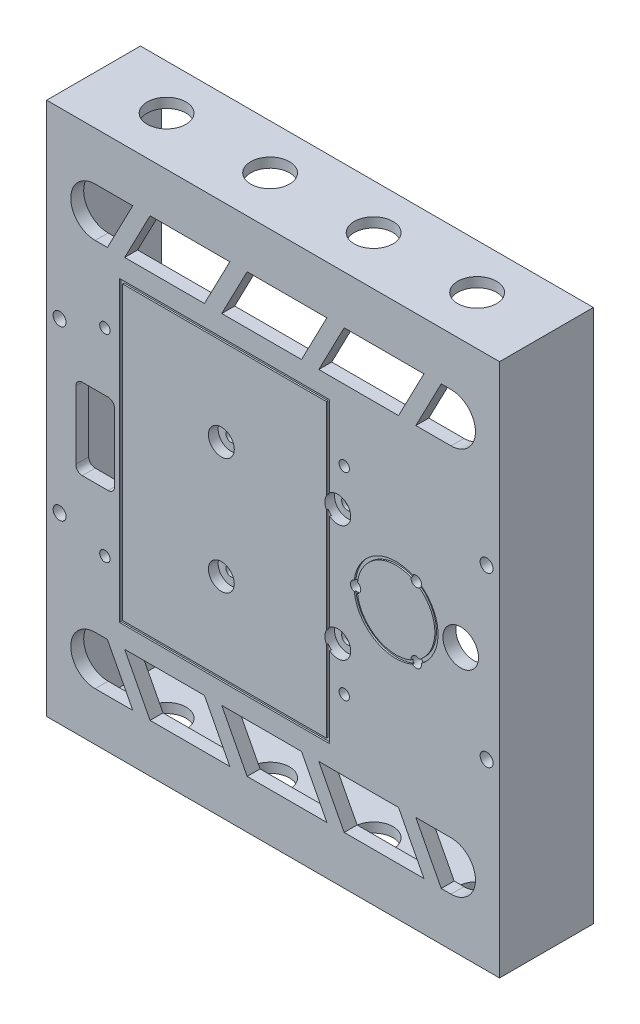
SolidWorks part; units mm, degrees
ref_plane "前视基准面" through (0, 0, 0) normal (0, 0, 1) x (1, 0, 0)
ref_plane "上视基准面" through (0, 0, 0) normal (0, 1, 0) x (1, 0, 0)
ref_plane "右视基准面" through (0, 0, 0) normal (1, 0, 0) x (0, 0, -1)
other "Configuration Table"
sketch "草图1" plane through (0, 0, 0) normal (0, 0, 1) x (1, 0, 0)
  line L0 (-109.8258, 0) -> (108.2292, 0) construction
  line L1 (-70, -82.5) -> (70, -82.5)
  line L2 (-70, -82.5) -> (-70, 82.5)
  line L3 (-70, 82.5) -> (70, 82.5)
  line L4 (70, -82.5) -> (70, 82.5)
  line L5 (-70, -82.5) -> (70, 82.5) construction
  line L6 (-70, 82.5) -> (70, -82.5) construction
  line L13 (-59, -12.5) -> (-51, -12.5)
  line L16 (0, 87.3901) -> (0, -88.6403) construction
  line L17 (-54.4075, -60) -> (62.7091, -60) construction
  line L20 (-61, -10.5) -> (-61, 10.5)
  line L21 (-59, 12.5) -> (-51, 12.5)
  line L22 (-49, -10.5) -> (-49, 10.5)
  line L23 (-61, -12.5) -> (-49, 12.5) construction
  line L24 (-61, 12.5) -> (-49, -12.5) construction
  line L107 (-50.0297, -53) -> (45.5374, -53) construction
  line L108 (-55, -60) -> (55, -60) construction
  line L109 (-55, -52.4529) -> (-51.2224, -52.4529)
  line L110 (-55, -67.5471) -> (-43.3736, -67.5471)
  line L112 (-51.2224, -52.4529) -> (-43.3736, -67.5471)
  line L113 (-45.8742, -52.4529) -> (-38.0254, -67.5471)
  line L116 (-21.2224, -52.4529) -> (-13.3736, -67.5471)
  line L118 (-15.8742, -52.4529) -> (-8.0254, -67.5471)
  line L120 (8.7776, -52.4529) -> (16.6264, -67.5471)
  line L122 (14.1258, -52.4529) -> (21.9746, -67.5471)
  line L124 (38.7776, -52.4529) -> (46.6264, -67.5471)
  line L126 (44.1258, -52.4529) -> (51.9746, -67.5471)
  line L127 (-45.8742, -52.4529) -> (-21.2224, -52.4529)
  line L128 (-38.0254, -67.5471) -> (-13.3736, -67.5471)
  line L129 (-8.0254, -67.5471) -> (16.6264, -67.5471)
  line L130 (-15.8742, -52.4529) -> (8.7776, -52.4529)
  line L131 (14.1258, -52.4529) -> (38.7776, -52.4529)
  line L132 (21.9746, -67.5471) -> (46.6264, -67.5471)
  line L133 (44.1258, -52.4529) -> (55, -52.4529)
  line L134 (51.9746, -67.5471) -> (55, -67.5471)
  line L135 (51.9746, 67.5471) -> (55, 67.5471)
  line L136 (44.1258, 52.4529) -> (51.9746, 67.5471)
  line L137 (44.1258, 52.4529) -> (55, 52.4529)
  line L138 (14.1258, 52.4529) -> (38.7776, 52.4529)
  line L139 (38.7776, 52.4529) -> (46.6264, 67.5471)
  line L140 (21.9746, 67.5471) -> (46.6264, 67.5471)
  line L141 (14.1258, 52.4529) -> (21.9746, 67.5471)
  line L142 (-15.8742, 52.4529) -> (8.7776, 52.4529)
  line L143 (8.7776, 52.4529) -> (16.6264, 67.5471)
  line L144 (-8.0254, 67.5471) -> (16.6264, 67.5471)
  line L145 (-15.8742, 52.4529) -> (-8.0254, 67.5471)
  line L146 (-45.8742, 52.4529) -> (-21.2224, 52.4529)
  line L147 (-21.2224, 52.4529) -> (-13.3736, 67.5471)
  line L148 (-38.0254, 67.5471) -> (-13.3736, 67.5471)
  line L149 (-45.8742, 52.4529) -> (-38.0254, 67.5471)
  line L150 (-55, 67.5471) -> (-43.3736, 67.5471)
  line L151 (-55, 52.4529) -> (-51.2224, 52.4529)
  line L152 (-51.2224, 52.4529) -> (-43.3736, 67.5471)
  line L153 (-16, 18) -> (20, 18) construction
  circle A5 centre (-66, 26) radius 2
  circle A10 centre (-66, -26) radius 2
  circle A15 centre (58, 0) radius 5.5
  arc A17 (-51, -12.5) -> (-49, -10.5) centre (-51, -10.5) ccw
  arc A18 (-59, -12.5) -> (-61, -10.5) centre (-59, -10.5) cw
  arc A19 (-51, 12.5) -> (-49, 10.5) centre (-51, 10.5) cw
  arc A20 (-61, 10.5) -> (-59, 12.5) centre (-59, 10.5) cw
  circle A24 centre (66, -26) radius 2
  circle A25 centre (66, 26) radius 2
  circle A29 centre (-16, 18) radius 1.6
  circle A35 centre (-52, 30.55) radius 1.6
  circle A37 centre (-52, -30.55) radius 1.6
  circle A41 centre (38, 0) radius 12.5 construction
  circle A42 centre (25.5, 0) radius 1.6
  circle A43 centre (44.25, 10.8253) radius 1.6
  circle A44 centre (44.25, -10.8253) radius 1.6
  arc A47 (-55, -52.4529) -> (-55, -67.5471) centre (-55, -60) ccw
  arc A48 (55, -67.5471) -> (55, -52.4529) centre (55, -60) ccw
  arc A49 (55, 67.5471) -> (55, 52.4529) centre (55, 60) cw
  arc A50 (-55, 52.4529) -> (-55, 67.5471) centre (-55, 60) cw
  circle A51 centre (20, 18) radius 1.8189
  circle A52 centre (20, -18) radius 1.8189
  circle A53 centre (-16, -18) radius 1.6
  circle A54 centre (22, 30.55) radius 1.6
  circle A55 centre (22, -30.55) radius 1.6
  point P0 (0, 0)
  point P12 (0, 0)
  point P13 (-55, 0)
  point P24 (0, 0)
  point P26 (0, -60)
  point P35 (0, 57)
  point P46 (0, -57)
  point P53 (38, 0)
  point P69 (0, 0)
  point P73 (38, 0)
  point P114 (0, 0)
  dimension "D3" = 26
  dimension "D6" = 38
  dimension "D7" = 4
  dimension "D8" = 9
  dimension "D10" = 25
  dimension "D11" = 70
  dimension "D12" = 3.2
  dimension "D13" = 2
  dimension "D14" = 3
  dimension "D15" = 25
  dimension "D17" = 18
  dimension "D18" = 36
  dimension "D21" = 4
  dimension "D22" = 74
  dimension "D23" = 3.2
  dimension "D24" = 30.55
  dimension "D25" = 18
  dimension "D26" = 58
  dimension "D28" = 4
  dimension "D29" = 11
  dimension "D19" = 16
  dimension "D1" = 140
  dimension "D2" = 165
  dimension "D9" = 12
  dimension "D20" = 60
  dimension "D16" = 82.5
extrude "凸台-拉伸1" add sketch "草图1" along normal blind 4
sketch "草图2" plane through (0, 0, 4) normal (0, 0, 1) x (1, 0, 0)
sketch "草图3" plane through (0, 0, 4) normal (0, 0, 1) x (1, 0, 0)
  line L1 (-47.5, 46.05) -> (17.5, 46.05)
  line L2 (-47.5, 46.05) -> (-47.5, -46.05)
  line L3 (-47.5, -46.05) -> (17.5, -46.05)
  line L4 (17.5, 46.05) -> (17.5, -46.05)
  line L5 (-46.5, 45.05) -> (16.5, 45.05)
  line L6 (-46.5, 45.05) -> (-46.5, -45.05)
  line L7 (-46.5, -45.05) -> (16.5, -45.05)
  line L8 (16.5, 45.05) -> (16.5, -45.05)
  circle A0 centre (-52, 30.55) radius 1.6 construction
  circle A2 centre (22, 30.55) radius 1.6 construction
  circle A3 centre (-52, -30.55) radius 1.6 construction
  dimension "D3" = 4.5
  dimension "D7" = 14.5
  dimension "D8" = 15.5
  dimension "D1" = 5.5
  dimension "D2" = 4.5
  dimension "D4" = 5.5
  dimension "D5" = 15.5
  dimension "D6" = 14.5
extrude "切除-拉伸2" cut sketch "草图3" against normal blind 0.5
sketch "草图4" plane through (0, 0, 4) normal (0, 0, 1) x (1, 0, 0)
  line L0 (0, 0) -> (86.3905, 0) construction
  circle A0 centre (38, 0) radius 12
  circle A1 centre (38, 0) radius 13
  dimension "D2" = 24
  dimension "D3" = 26
  dimension "D1" = 38
extrude "切除-拉伸3" cut sketch "草图4" against normal blind 0.5
sketch "草图5" plane through (0, 0, 0) normal (0, 0, -1) x (-1, 0, 0)
  line L1 (-70, 82.5) -> (70, 82.5)
  line L2 (-70, 82.5) -> (-70, -82.5)
  line L3 (-70, -82.5) -> (70, -82.5)
  line L4 (70, 82.5) -> (70, -82.5)
  line L5 (-63.5, -79.5) -> (63.5, -79.5)
  line L6 (-63.5, -79.5) -> (-63.5, 79.5)
  line L7 (-63.5, 79.5) -> (63.5, 79.5)
  line L8 (63.5, -79.5) -> (63.5, 79.5)
  line L9 (-63.5, -79.5) -> (63.5, 79.5) construction
  line L10 (-63.5, 79.5) -> (63.5, -79.5) construction
  circle A0 centre (66, 26) radius 1.9625
  circle A1 centre (66, -26) radius 2
  circle A2 centre (-66, 26) radius 2
  circle A3 centre (-66, -26) radius 2
  point P6 (0, 0)
  dimension "D1" = 6.5
  dimension "D2" = 3
extrude "凸台-拉伸2" add sketch "草图5" along normal blind 25
sketch "草图9" plane through (0, 82.5, 0) normal (0, 1, 0) x (1, 0, 0)
sketch "草图10" plane through (-70, 0, 0) normal (-1, 0, 0) x (0, 0, 1)
  line L0 (-14, 82.5) -> (-14, -82.5) construction
  line L1 (4, 82.5) -> (-25, 82.5) construction
  line L2 (4, -82.5) -> (-25, -82.5) construction
  line L3 (-25, -82.5) -> (-25, 82.5) construction
  text T1 "Hohai University" font "方正舒体" height in points 22
  dimension "D1" = 11
extrude "切除-拉伸7" cut sketch "草图10" against normal blind 1
sketch "草图11" plane through (0, 82.5, 0) normal (0, 1, 0) x (1, 0, 0)
  line L0 (-70, 11.077) -> (70, 11.077) construction
  line L1 (70, -4) -> (70, 25) construction
  line L2 (0, 40.987) -> (0, -25.4503) construction
  circle A0 centre (-48, 11.077) radius 6
  circle A1 centre (-16, 11.077) radius 6
  circle A2 centre (48, 11.077) radius 6
  circle A3 centre (16, 11.077) radius 6
  dimension "D1" = 16
  dimension "D2" = 48
extrude "切除-拉伸8" cut sketch "草图11" against normal through all both and the other way through all
sketch "草图12" plane through (0, 0, 4) normal (0, 0, 1) x (1, 0, 0)
  circle A0 centre (-16, 18) radius 4
  circle A1 centre (-16, -18) radius 4
  circle A2 centre (20, 18) radius 4
  circle A3 centre (20, -18) radius 4
extrude "切除-拉伸9" cut sketch "草图12" against normal blind 3
